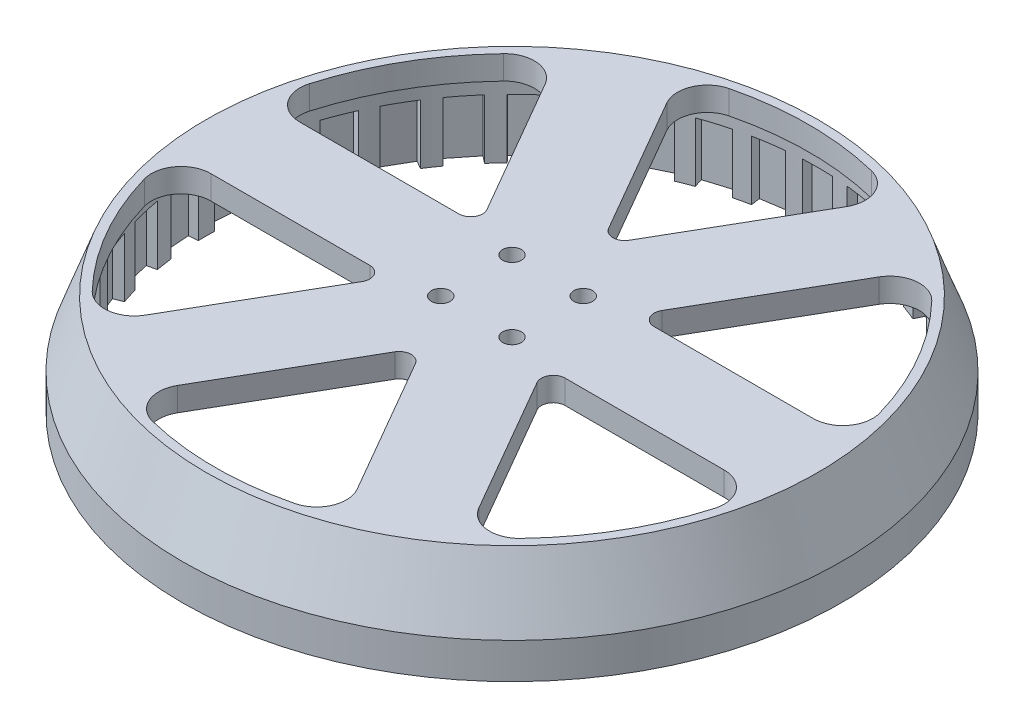
SolidWorks part; units mm, degrees
material "ABS"
ref_plane "Front Plane" through (0, 0, 0) normal (0, 0, 1) x (1, 0, 0)
ref_plane "Top Plane" through (0, 0, 0) normal (0, 1, 0) x (1, 0, 0)
ref_plane "Right Plane" through (0, 0, 0) normal (1, 0, 0) x (0, 0, -1)
sketch "Sketch1" plane through (0, 0, 0) normal (0, 0, 1) x (1, 0, 0)
  line L0 (0, 29) -> (0, 33)
  line L4 (51.5, 29) -> (51.5, 16)
  line L5 (51.5, 16) -> (55.5, 16)
  line L6 (55.5, 16) -> (55.5, 33)
  line L7 (55.5, 33) -> (0, 33)
  line L8 (0, 0) -> (0, 63.0003) construction
  line L11 (0, 29) -> (51.5, 29)
  dimension "D3" = 103
  dimension "D4" = 4
  dimension "D7" = 13
  dimension "D8" = 4
revolve "Main Revolve" add sketch "Sketch1" angle 360 about L8
sketch "Sketch2" plane through (0, 33, 0) normal (0, 1, 0) x (1, 0, 0)
  line L0 (0, 0) -> (0, 75.8468) construction
  line L1 (0, 0) -> (27.75, 48.0644) construction
  line L2 (15.1193, 41.1874) -> (1.7321, 18)
  line L3 (-15.1193, 41.1874) -> (-1.7321, 18)
  line L4 (0, 0) -> (-27.75, 48.0644) construction
  arc A0 (-11.988, 48.5416) -> (11.988, 48.5416) centre (0, 0) cw
  circle A2 centre (0, 0) radius 55.5 construction
  arc A3 (11.988, 48.5416) -> (15.1193, 41.1874) centre (10.7892, 43.6874) cw
  arc A6 (-11.988, 48.5416) -> (-15.1193, 41.1874) centre (-10.7892, 43.6874) ccw
  arc A7 (1.7321, 18) -> (-1.7321, 18) centre (0, 19) cw
  point P15 (0, 15)
  dimension "D5" = 50
  dimension "D6" = 2
  dimension "D7" = 5
  dimension "D3" = 5
  dimension "D1" = 30
  dimension "D2" = 30
  dimension "D4" = 15
extrude "Slot Cut" cut sketch "Sketch2" against normal through all
pattern_circular "Slot Cut Pattern" count 6 over 360 about axis through (0, 33, 0) along (0, -1, 0) of "Slot Cut"
sketch "Sketch4" plane through (0, 16, 0) normal (0, -1, 0) x (1, 0, 0)
  line L0 (-2.5, 53) -> (2.5, 53)
  line L1 (-2.5, 53) -> (-2.5, 51.4393)
  line L2 (2.5, 53) -> (2.5, 51.4393)
  circle A0 centre (0, 0) radius 51.5 construction
  arc A1 (2.5, 51.4393) -> (-2.5, 51.4393) centre (0, 0) ccw
  point P3 (0, 53)
  dimension "D2" = 1.5
  dimension "D1" = 5
extrude "Magnet Slots" cut sketch "Sketch4" against normal blind 10
pattern_circular "Magnet Cut Pattern" count 42 over 360 about axis through (0, 16, 0) along (0, -1, 0) of "Magnet Slots"
sketch "Sketch5" plane through (0, 33, 0) normal (0, 1, 0) x (1, 0, 0)
  line L1 (-6, -6) -> (6, -6) construction
  line L2 (-6, -6) -> (-6, 6) construction
  line L3 (-6, 6) -> (6, 6) construction
  line L4 (6, -6) -> (6, 6) construction
  line L5 (-6, -6) -> (6, 6) construction
  line L6 (-6, 6) -> (6, -6) construction
  circle A0 centre (-6, 6) radius 1.575
  circle A1 centre (-6, 6) radius 3
  circle A2 centre (6, 6) radius 3
  circle A3 centre (6, 6) radius 1.575
  circle A4 centre (6, -6) radius 3
  circle A5 centre (6, -6) radius 1.575
  circle A6 centre (-6, -6) radius 3
  circle A7 centre (-6, -6) radius 1.575
  point P0 (0, 0)
  point P11 (0, 0)
  point P15 (0, 0)
  point P19 (0, 0)
  point P23 (0, 0)
  dimension "D4" = 4
  dimension "D2" = 3.15
  dimension "D3" = 6
  dimension "D1" = 12
extrude "Cut-Extrude1" cut sketch "Sketch5" against normal blind 10 contours A0 | A3 | A5 | A7
chamfer "Chamfer1" distance 4 angle 70 1 edges at (0, 33, -55.5) first distance on face at (-6, 33, 7.575)
equation "\"D3@Sketch1\"=100+2*(1+0.5)"
equation "\"D2@Sketch5\"=3.15"
